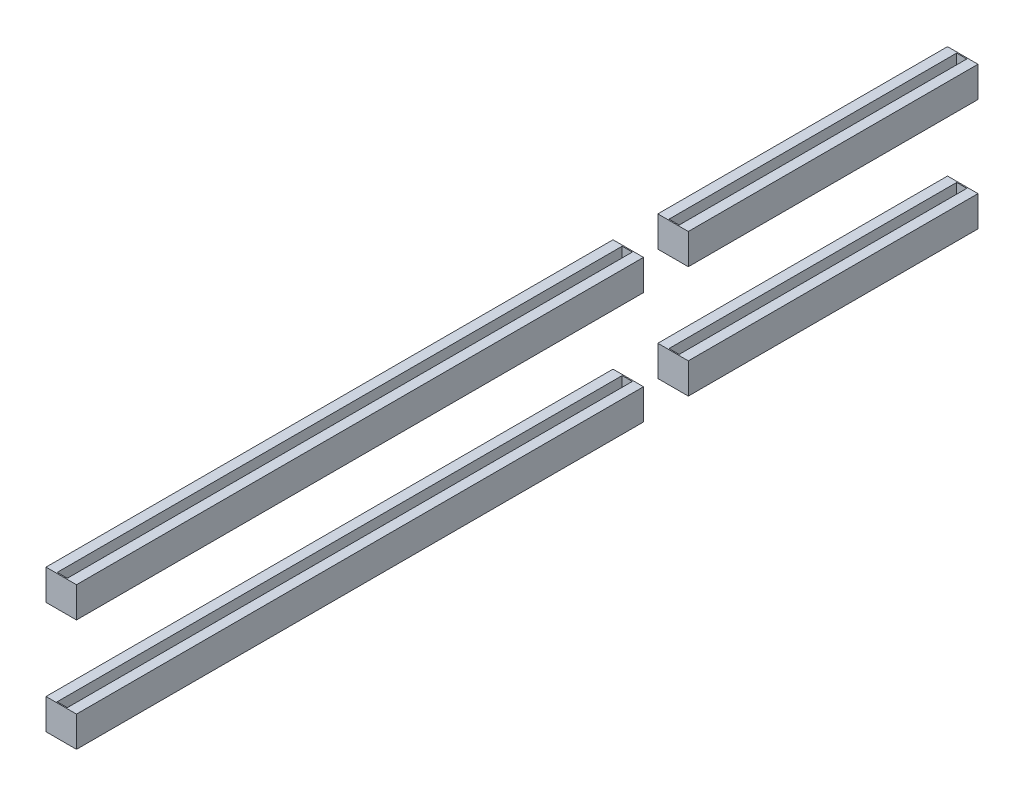
SolidWorks part; units mm, degrees
ref_plane "Front Plane" through (0, 0, 0) normal (0, 0, 1) x (1, 0, 0)
ref_plane "Top Plane" through (0, 0, 0) normal (0, 1, 0) x (1, 0, 0)
ref_plane "Right Plane" through (0, 0, 0) normal (1, 0, 0) x (0, 0, -1)
sketch "Sketch1" plane through (0, 0, 0) normal (0, 0, 1) x (1, 0, 0)
  line L0 (419.4943, -272.1944) -> (394.1831, -272.1944)
  line L5 (394.1831, -272.1944) -> (394.1831, -246.8145)
  line L6 (419.4943, -272.1944) -> (419.4943, -195.9944)
  line L8 (343.4719, -272.1944) -> (343.4719, -195.9944)
  line L10 (419.4943, -195.9944) -> (394.1831, -195.9944)
  line L11 (394.1831, -246.8145) -> (368.7831, -246.8145)
  line L12 (394.1831, -195.9944) -> (394.1831, -221.3743)
  line L13 (368.7831, -195.9944) -> (368.7831, -221.3743)
  line L14 (368.7831, -272.1944) -> (368.7831, -246.8145)
  line L15 (394.1831, -221.3743) -> (368.7831, -221.3743)
  line L16 (368.7831, -195.9944) -> (343.4719, -195.9944)
  line L17 (368.7831, -272.1944) -> (343.4719, -272.1944)
  line L20 (368.7831, 83.4056) -> (343.4719, 83.4056)
  line L21 (368.7831, 7.2056) -> (343.4719, 7.2056)
  line L22 (394.1831, 32.5855) -> (368.7831, 32.5855)
  line L23 (368.7831, 83.4056) -> (368.7831, 58.0257)
  line L24 (368.7831, 7.2056) -> (368.7831, 32.5855)
  line L25 (394.1831, 7.2056) -> (394.1831, 32.5855)
  line L26 (394.1831, 58.0257) -> (368.7831, 58.0257)
  line L27 (419.4943, 7.2056) -> (394.1831, 7.2056)
  line L28 (343.4719, 83.4056) -> (343.4719, 7.2056)
  line L29 (419.4943, 83.4056) -> (419.4943, 7.2056)
  line L30 (394.1831, 83.4056) -> (394.1831, 58.0257)
  line L31 (419.4943, 83.4056) -> (394.1831, 83.4056)
extrude "Boss-Extrude3" add sketch "Sketch1" along normal blind 2248.154 contours L8 L16 L13 L15 L12 L10 L6 L0 L5 L11 L14 L17 | L20 L28 L21 L24 L22 L25 L27 L29 L31 L30 L26 L23
sketch "Sketch5" plane through (0, 0, 0) normal (0, 0, 1) x (1, 0, 0)
  line L2 (394.2719, -183.2944) -> (394.2719, -75.3444)
  line L7 (394.2719, -75.3444) -> (422.1006, -75.3444)
  line L8 (392.4177, -272.1944) -> (392.4177, -183.2944)
  line L9 (370.5897, -272.1944) -> (392.4177, -272.1944)
  line L10 (392.4177, 32.6056) -> (388.5226, 32.6056)
  line L11 (392.4177, 121.5056) -> (392.4177, 32.6056)
  line L12 (370.5897, 121.5056) -> (392.4177, 121.5056)
  line L13 (392.4177, -183.2944) -> (388.5226, -183.2944)
  spline S0 degree 3 poles (370.5897, -272.1944) (374.1461, -261.2725) (378.0408, -246.563) (381.9461, -227.6895) (385.2742, -209.1814) (387.3502, -194.2426) (388.5226, -183.2944) knots 0 0 0 0 0.379013 0.502092 0.636438 1 1 1 1
  spline S4 degree 3 poles (370.5897, 121.5056) (374.1461, 110.5837) (378.0408, 95.8742) (381.9461, 77.0007) (385.2742, 58.4926) (387.3502, 43.5538) (388.5226, 32.6056) knots 0 0 0 0 0.379013 0.502092 0.636438 1 1 1 1
  point P15 (0, 0)
  point P20 (0, 0)
extrude "Cut-Extrude2" [suppressed] cut sketch "Sketch5" along normal through all contours L10 S4 L12 L11 | L8 L13 S0 L9
ref_plane "Plane2" through (0, 0, 0) normal (0, 0, -1) x (-1, 0, 0)
sketch "Sketch9" plane through (0, 0, 0) normal (0, 0, -1) x (-1, 0, 0)
  line L6 (-394.1831, -272.1944) -> (-368.7831, -272.1944)
  line L7 (-368.7831, -272.1944) -> (-368.7831, -195.9944)
  line L8 (-368.7831, -195.9944) -> (-394.1831, -195.9944)
  line L13 (-394.1831, -195.9944) -> (-394.1831, -272.1944)
  line L14 (-394.1831, 7.2056) -> (-368.7831, 7.2056)
  line L15 (-368.7831, 7.2056) -> (-368.7831, 83.4056)
  line L16 (-368.7831, 83.4056) -> (-394.1831, 83.4056)
  line L17 (-394.1831, 83.4056) -> (-394.1831, 7.2056)
extrude "Boss-Extrude4" add sketch "Sketch9" against normal blind 2.54 separate body contours L6 L7 L8 L13 | L17 L14 L15 L16
ref_plane "Plane3" through (0, 0, 2248.154) normal (0, 0, 1) x (1, 0, 0)
sketch "Sketch11" plane through (0, 0, 2248.154) normal (0, 0, 1) x (1, 0, 0)
  line L0 (394.1831, 83.4056) -> (368.7831, 83.4056)
  line L1 (368.7831, 83.4056) -> (368.7831, 7.2056)
  line L2 (368.7831, 7.2056) -> (394.1831, 7.2056)
  line L3 (394.1831, 7.2056) -> (394.1831, 83.4056)
  line L4 (394.1831, -195.9944) -> (368.7831, -195.9944)
  line L5 (368.7831, -195.9944) -> (368.7831, -272.1944)
  line L6 (368.7831, -272.1944) -> (394.1831, -272.1944)
  line L7 (394.1831, -272.1944) -> (394.1831, -195.9944)
extrude "Boss-Extrude8" add sketch "Sketch11" against normal blind 2.54 contours L6 L7 L4 L5 | L3 L0 L1 L2 region at (381.4831, -234.0944, 2248.154)
ref_plane "Plane4" through (0, 183.4056, 0) normal (0, 1, 0) x (1, 0, 0)
sketch "Sketch14" plane through (0, 183.4056, 0) normal (0, 1, 0) x (1, 0, 0)
  line L0 (339.5659, -834.1608) -> (339.5659, -722.4008)
  line L1 (342.1228, -834.1608) -> (465.4958, -834.1608) construction
  line L2 (465.4958, -722.4008) -> (342.1228, -722.4008) construction
  line L3 (339.5659, -722.4008) -> (419.4943, -722.4008)
  line L4 (419.4943, -2248.154) -> (419.4943, 0) construction
  line L5 (419.4943, -722.4008) -> (419.4943, -834.1608)
  line L6 (419.4943, -834.1608) -> (339.5659, -834.1608)
extrude "Cut-Extrude5" cut sketch "Sketch14" against normal through all
ref_plane "Plane5" through (0, 0, 834.1608) normal (0, 0, -1) x (-1, 0, 0)
sketch "Sketch15" plane through (0, 0, 834.1608) normal (0, 0, -1) x (-1, 0, 0)
  line L0 (-394.1831, -272.1944) -> (-368.7831, -272.1944)
  line L1 (-368.7831, -272.1944) -> (-368.7831, -195.9944)
  line L2 (-368.7831, -195.9944) -> (-394.1831, -195.9944)
  line L3 (-394.1831, -195.9944) -> (-394.1831, -272.1944)
  line L4 (-394.1831, 7.2056) -> (-394.1831, 83.4056)
  line L5 (-394.1831, 83.4056) -> (-368.7831, 83.4056)
  line L6 (-368.7831, 83.4056) -> (-368.7831, 7.2056)
  line L7 (-368.7831, 7.2056) -> (-394.1831, 7.2056)
extrude "Boss-Extrude9" add sketch "Sketch15" against normal blind 2.54 contours L7 L6 L5 L4 | L3 L0 L1 L2 region at (381.4831, 45.3056, 834.1608)
ref_plane "Plane6" through (0, 0, 722.4008) normal (0, 0, 1) x (1, 0, 0)
sketch "Sketch16" plane through (0, 0, 722.4008) normal (0, 0, 1) x (1, 0, 0)
  line L0 (394.1831, 83.4056) -> (368.7831, 83.4056)
  line L1 (368.7831, 83.4056) -> (368.7831, 7.2056)
  line L2 (368.7831, 7.2056) -> (394.1831, 7.2056)
  line L3 (394.1831, 7.2056) -> (394.1831, 83.4056)
  line L4 (394.1831, -272.1944) -> (368.7831, -272.1944)
  line L5 (368.7831, -272.1944) -> (368.7831, -195.9944)
  line L6 (368.7831, -195.9944) -> (394.1831, -195.9944)
  line L7 (394.1831, -195.9944) -> (394.1831, -272.1944)
extrude "Boss-Extrude10" add sketch "Sketch16" against normal blind 2.54 contours L7 L6 L5 L4 | L3 L0 L1 L2 region at (381.4831, -234.0944, 722.4008)
ref_plane "Plane1" through (0, 124.0456, 0) normal (0, 1, 0) x (1, 0, 0)
sketch "Sketch7" [suppressed] plane through (0, 124.0456, 0) normal (0, 1, 0) x (1, 0, 0)
  line L0 (370.5897, -2552.192) -> (370.5897, 0) construction
  line L4 (382.0193, -434.8941) -> (381.5719, 0)
  line L5 (381.5719, 0) -> (343.4719, 0)
  spline S0 degree 3 poles (382.0193, -434.8941) (376.3305, -358.6722) (371.6757, -282.3808) (366.8414, -206.1021) knots 0 0 0 0 1 1 1 1
  spline S1 degree 3 poles (374.469, -326.0797) (374.7194, -329.4636) (375.2175, -336.2346) (375.9564, -346.3957) (376.6796, -356.5522) (377.3925, -366.7015) (378.0959, -376.8367) (378.7891, -386.948) (379.4733, -397.0221) (380.1486, -407.0413) (380.8149, -416.9762) (381.3623, -425.1403) (381.7942, -431.5626) (382.1144, -436.3039) (382.4298, -440.9461) (382.7387, -445.4516) (383.0383, -449.7748) (383.3242, -453.8501) (383.5909, -457.5964) (383.8304, -460.9132) (384.0004, -463.2412) (384.1148, -464.8003) (384.1884, -465.7996) (384.2488, -466.6142) (384.2953, -467.2361) (384.3218, -467.5865) (384.3364, -467.7815) (384.3415, -467.8534) (384.3438, -467.8883) knots 0.766367 0.766367 0.766367 0.766367 0.78078 0.795194 0.809607 0.824021 0.838435 0.852848 0.867262 0.881675 0.896089 0.910502 0.917709 0.924916 0.932123 0.939329 0.946536 0.953743 0.96095 0.968156 0.975363 0.978967 0.98257 0.986173 0.989777 0.99338 0.995182 0.996983 0.996983 0.996983 0.996983 construction
  spline S2 degree 2 poles (366.8414, -206.1021) (362.2604, -102.3348) (343.4719, 0) knots 0 0 0 1 1 1
extrude "Cut-Extrude4" [suppressed] cut sketch "Sketch7" against normal blind 508
